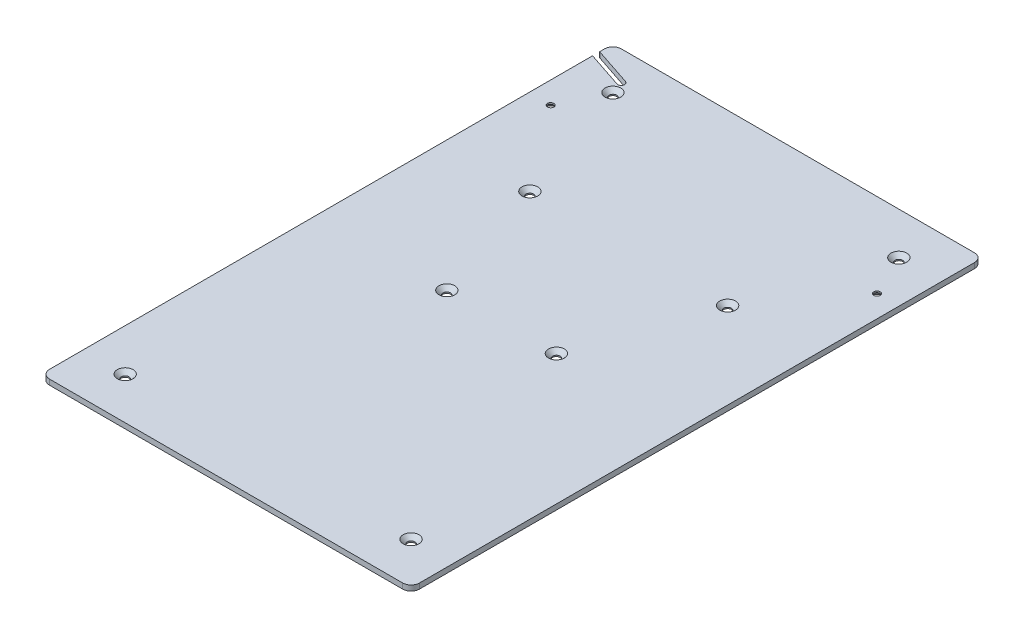
SolidWorks part; units mm, degrees
material "Acrylic (Medium-high impact)"
ref_plane "Front Plane" through (0, 0, 0) normal (0, 0, 1) x (1, 0, 0)
ref_plane "Top Plane" through (0, 0, 0) normal (0, 1, 0) x (1, 0, 0)
ref_plane "Right Plane" through (0, 0, 0) normal (1, 0, 0) x (0, 0, -1)
sketch "Sketch1" plane through (0, 0, 0) normal (0, 1, 0) x (1, 0, 0)
  line L0 (0, -170) -> (0, 170) construction
  line L1 (-110, 170) -> (110, 170)
  line L2 (-110, 170) -> (-110, -170)
  line L3 (-110, -170) -> (110, -170)
  line L4 (110, 170) -> (110, -170)
  line L5 (110, 0) -> (-110, 0) construction
  dimension "D1" = 340
  dimension "D2" = 220
extrude "Boss-Extrude1" add sketch "Sketch1" along normal blind 3.175
fillet "Fillet1" radius 5 4 edges at (110, 1.5875, -170) (-110, 1.5875, -170) (-110, 1.5875, 170) (110, 1.5875, 170)
hole_wizard "CSK for #6 Flat Head Socket Cap Screw1" positions "Sketch3" profile "Sketch4" countersink size "#6" standard "Ansi Inch" end condition through all
sketch "Sketch3" plane through (0, 0, 0) normal (0, -1, 0) x (1, 0, 0)
  line L4 (0, -170) -> (0, 0) construction
  line L5 (105, -170) -> (-105, -170) construction
  line L7 (97, -120) -> (0, -120) construction
  line L9 (0, -120) -> (-97, -120) construction
  point P0 (97, -120)
  point P1 (-97, -120)
  dimension "D1" = 97
  dimension "D2" = 50
sketch "Sketch4" plane through (97, 0, -120) normal (1, 0, 0) x (0, 0, -1)
  line L0 (0, 0) -> (0, 3.175)
  line L1 (0, 3.175) -> (1.8986, 3.175)
  line L2 (1.8986, 3.175) -> (1.8986, 2.301)
  line L3 (1.8986, 2.301) -> (3.8989, 0)
  line L5 (3.8989, 0) -> (0, 0)
  line L6 (-1.8987, 2.301) -> (-3.8989, 0) construction
  line L11 (0, -6.35) -> (0, 107.95) construction
  dimension "Thru Hole Dia." = 3.7973
  dimension "Thru Hole Depth" = 3.175
  dimension "Near C'Sink Dia." = 7.7978
  dimension "Near C'Sink Angle" = 82
hole_wizard "CSK for M4 Flat Head Machine Screw1" positions "Sketch6" profile "Sketch5" countersink size "M4" standard "Ansi Metric" end condition through all
sketch "Sketch6" plane through (0, 3.175, 0) normal (0, 1, 0) x (-1, 0, 0)
  line L0 (0, 170) -> (0, 100) construction
  line L1 (105, 170) -> (-105, 170) construction
  line L3 (0, 100) -> (85, 145) construction
  line L5 (0, 100) -> (85, -145) construction
  line L7 (110, -165) -> (110, 165) construction
  line L8 (-105, -170) -> (105, -170) construction
  point P0 (85, 145)
  point P1 (32.5564, 6.1611)
  point P3 (58.7782, -69.4195)
  point P5 (85, -145)
  dimension "D1" = 70
  dimension "D2" = 25
  dimension "D3" = 25
  dimension "D4" = 25
  dimension "D5" = 25
  dimension "D6" = 80
  dimension "D7" = 80
sketch "Sketch5" plane through (-85, 3.175, 145) normal (1, 0, 0) x (0, 0, 1)
  line L0 (0, 0) -> (0, 3.175)
  line L1 (0, 3.175) -> (2.25, 3.175)
  line L2 (2.25, 3.175) -> (2.25, 2.45)
  line L3 (2.25, 2.45) -> (4.7, 0)
  line L5 (4.7, 0) -> (0, 0)
  line L6 (-2.25, 2.45) -> (-4.7, 0) construction
  line L11 (0, -6.35) -> (0, 107.95) construction
  dimension "Thru Hole Dia." = 4.5
  dimension "Thru Hole Depth" = 3.175
  dimension "Near C'Sink Dia." = 9.4
  dimension "Near C'Sink Angle" = 90
mirror "Mirror1" about plane through (0, 0, 0) normal (1, 0, 0) of "CSK for M4 Flat Head Machine Screw1"
sketch "Sketch7" plane through (0, 3.175, 0) normal (0, 1, 0) x (1, 0, 0)
  line L0 (-110, 160) -> (-87.6222, 152.5581) construction
  line L1 (-110, 165) -> (-110, -165) construction
  line L2 (-109.3689, 161.8978) -> (-86.991, 154.4559)
  line L3 (-110.6311, 158.1022) -> (-88.2533, 150.6602)
  line L4 (0, -100) -> (-85, 145) construction
  line L5 (0, -100) -> (-85, 145) construction
  line L6 (-85, 145) -> (-87.6222, 152.5581) construction
  arc A0 (-109.3689, 161.8978) -> (-110.6311, 158.1022) centre (-110, 160) ccw
  arc A1 (-88.2533, 150.6602) -> (-86.991, 154.4559) centre (-87.6222, 152.5581) ccw
  circle A2 centre (-85, 145) radius 4.7 construction
  point P4 (-98.8111, 156.279)
  dimension "D1" = 2
  dimension "D2" = 8
  dimension "D3" = 5
extrude "Cut-Extrude1" cut sketch "Sketch7" against normal through all
